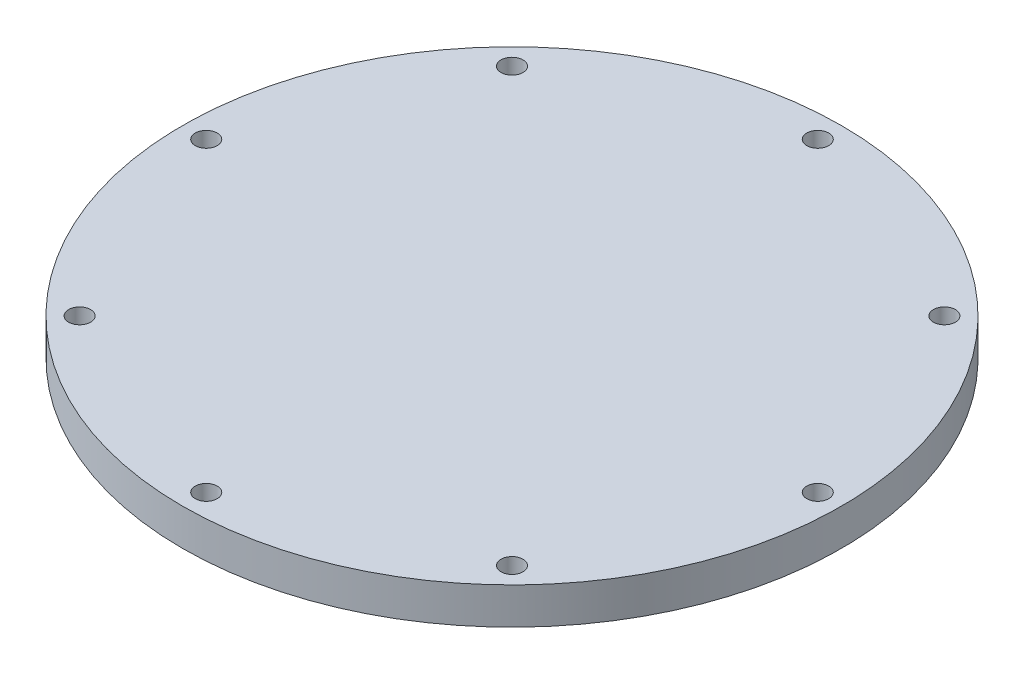
SolidWorks part; units mm, degrees
material "6061-T6 (SS)"
ref_plane "Front Plane" through (0, 0, 0) normal (0, 0, 1) x (1, 0, 0)
ref_plane "Top Plane" through (0, 0, 0) normal (0, 1, 0) x (1, 0, 0)
ref_plane "Right Plane" through (0, 0, 0) normal (1, 0, 0) x (0, 0, -1)
sketch "Sketch1" plane through (0, 0, 0) normal (0, 1, 0) x (1, 0, 0)
  circle A0 centre (0, 0) radius 45
  circle A1 centre (0, 41.75) radius 1.5
  circle A2 centre (29.5217, 29.5217) radius 1.5
  circle A3 centre (41.75, 0) radius 1.5
  circle A4 centre (29.5217, -29.5217) radius 1.5
  circle A5 centre (0, -41.75) radius 1.5
  circle A6 centre (-29.5217, -29.5217) radius 1.5
  circle A7 centre (-41.75, 0) radius 1.5
  circle A8 centre (-29.5217, 29.5217) radius 1.5
  point P22 (0, 0)
  dimension "D1" = 8
extrude "Boss-Extrude2" add sketch "Sketch1" along normal blind 5
